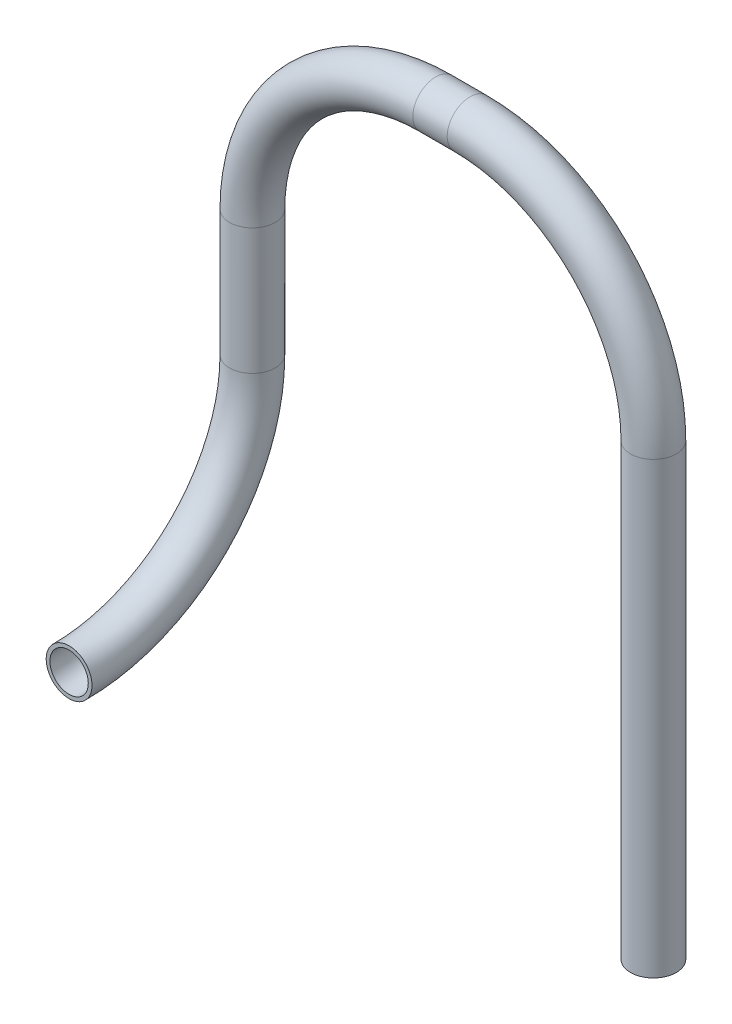
SolidWorks part; units mm, degrees
ref_plane "Front" through (0, 0, 0) normal (0, 0, 1) x (1, 0, 0)
ref_plane "Top" through (0, 0, 0) normal (0, 1, 0) x (1, 0, 0)
ref_plane "Right" through (0, 0, 0) normal (1, 0, 0) x (0, 0, -1)
sketch "Sketch1" plane through (0, 0, 0) normal (0, 0, 1) x (1, 0, 0)
  line L0 (70, 22) -> (70, -56.4)
  line L1 (0, 0) -> (0, 22)
  line L2 (32, 22) -> (32, 54) construction
  line L3 (32, 54) -> (38, 54)
  line L4 (38, 22) -> (70, 22) construction
  line L5 (38, 22) -> (38, 54) construction
  arc A0 (32, 54) -> (0, 22) centre (32, 22) ccw
  arc A1 (70, 22) -> (38, 54) centre (38, 22) ccw
  dimension "D2" = 32
  dimension "D6" = 32
  dimension "D1" = 22
  dimension "D4" = 78.4
  dimension "D5" = 6
sketch "Sketch2" plane through (0, 0, 0) normal (0, 1, 0) x (1, 0, 0)
  circle A0 centre (0, 0) radius 4
  dimension "D1" = 8
sketch "Sketch3" plane through (0, 0, 0) normal (1, 0, 0) x (0, 0, -1)
  line L0 (-32, 0) -> (-32, -32) construction
  arc A0 (-32, -32) -> (0, 0) centre (-32, 0) ccw
  dimension "D1" = 64
  dimension "D2" = 90
sketch "Sketch4" [suppressed] plane through (0, 0, 0) normal (0, 1, 0) x (1, 0, 0)
  circle A0 centre (0, 0) radius 3.35
  dimension "D1" = 6.7
sweep "Sweep-Thin1" add profiles "Sketch2" path "Sketch1" parameters "D1"=0.65
sweep "Sweep-Thin2" add profiles "Sketch2<6>" path "Sketch3" parameters "D1"=0.65
sketch "Sketch2<6>" plane through (0, 0, 0) normal (0, 1, 0) x (1, 0, 0) same geometry as "Sketch2"
